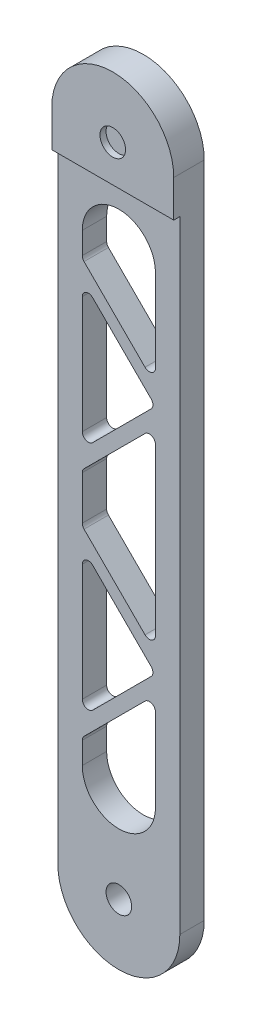
SolidWorks part; units mm, degrees
material "PLA"
ref_plane "Alzado" through (0, 0, 0) normal (0, 0, 1) x (1, 0, 0)
ref_plane "Planta" through (0, 0, 0) normal (0, 1, 0) x (1, 0, 0)
ref_plane "Vista lateral" through (0, 0, 0) normal (1, 0, 0) x (0, 0, -1)
sketch "Croquis1" plane through (0, 0, 0) normal (0, 0, 1) x (1, 0, 0)
  line L0 (0, 54) -> (0, -54) construction
  line L1 (10, 54) -> (10, -54)
  line L2 (-10, 54) -> (-10, -54)
  line L3 (0, 38) -> (0, -38) construction
  line L4 (6, 38) -> (6, -38)
  line L5 (-6, 38) -> (-6, -38)
  line L6 (-10, -47.95) -> (10, -47.95)
  line L7 (0, 51.9) -> (0, 44) construction
  line L8 (-10, 47.95) -> (10, 47.95)
  line L9 (0, -51.9) -> (0, -44) construction
  line L10 (0, 0) -> (0, -38) construction
  line L11 (-6, 0) -> (6, 0) construction
  line L12 (-6, -34) -> (6, -22)
  line L13 (-6, -31) -> (6, -19)
  line L14 (-6, -19) -> (6, -19) construction
  line L16 (-6, -7) -> (6, -19)
  line L17 (-6, -4) -> (6, -16)
  line L18 (-6, 4) -> (6, 16)
  line L19 (-6, 7) -> (6, 19)
  line L20 (-6, 31) -> (6, 19)
  line L21 (-6, 34) -> (6, 22)
  arc A0 (10, 54) -> (-10, 54) centre (0, 54) ccw
  arc A1 (-10, -54) -> (10, -54) centre (0, -54) ccw
  circle A2 centre (0, 54) radius 2.1
  circle A3 centre (0, -54) radius 2.1
  arc A4 (6, 38) -> (-6, 38) centre (0, 38) ccw
  arc A5 (-6, -38) -> (6, -38) centre (0, -38) ccw
  point P2 (0, 0)
  point P14 (0, 0)
  point P23 (0, 47.95)
  point P28 (0, -47.95)
  point P37 (0, -19)
  dimension "D1" = 4.2
  dimension "D2" = 20
  dimension "D3" = 108
  dimension "D4" = 4
  dimension "D5" = 16
  dimension "D6" = 135
  dimension "D7" = 3
extrude "Saliente-Extruir1" add sketch "Croquis1" along normal blind 4 contours L2 A1 L1 L8 A5 L5 A4 L4 A3 | L13 L5 L12 L4 | L17 L5 L16 L4 | L19 L5 L18 L4 | L21 L5 L20 L4 | L2 A1 L1 A0 | A3 | L5 A5 L4 A4 region at (9.0204, 0, 0) region at (0, 26.5, 0) region at (0, 11.5, 0) region at (0, -11.5, 0) region at (0, -26.5, 0)
extrude "Saliente-Extruir3" add sketch "Croquis1<6>" along normal blind 5 contours L1 A0 L2 L8 A2 region at (9.7436, 50.975, 0)
sketch "Croquis1<6>" plane through (0, 0, 0) normal (0, 0, 1) x (1, 0, 0) same geometry as "Croquis1"
fillet "Redondeo1" radius 1 14 edges at (6, 22, 2) (6, 16, 2) (6, 19, 2) (-6, 31, 2) (-6, 7, 2) (6, -22, 2) (6, -16, 2) (6, -19, 2) (-6, -31, 2) (-6, -7, 2) (-6, 34, 2) (-6, -4, 2) (-6, -34, 2) (-6, 4, 2)
